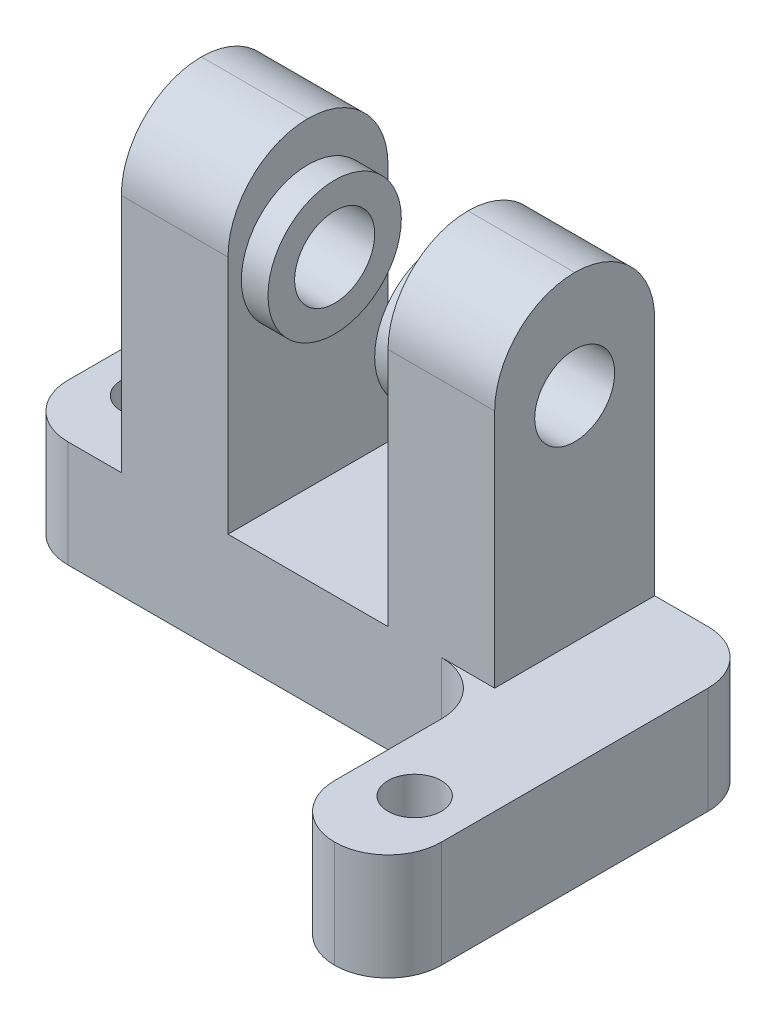
SolidWorks part; units mm, degrees
ref_plane "Front Plane" through (0, 0, 0) normal (0, 0, 1) x (1, 0, 0)
ref_plane "Top Plane" through (0, 0, 0) normal (0, 1, 0) x (1, 0, 0)
ref_plane "Right Plane" through (0, 0, 0) normal (1, 0, 0) x (0, 0, -1)
sketch "Sketch2" plane through (0, 0, 0) normal (0, 1, 0) x (1, 0, 0)
  line L1 (-7, 3) -> (7, 3)
  line L2 (-7, 3) -> (-7, -3)
  line L3 (-7, -3) -> (7, -3)
  line L4 (7, 3) -> (7, -3)
  line L5 (-7, 3) -> (7, -3) construction
  line L6 (-7, -3) -> (7, 3) construction
  point P0 (0, 0)
extrude "Boss-Extrude1" add sketch "Sketch2" along normal blind 4
sketch "Sketch3" plane through (0, 4, 0) normal (0, 1, 0) x (1, 0, 0)
  line L0 (-7, -3) -> (-3, -3)
  line L1 (-7, -3) -> (7, -3) construction
  line L2 (-3, -3) -> (-3, 3)
  line L3 (7, 3) -> (-7, 3) construction
  line L4 (-3, 3) -> (-7, 3)
  line L5 (-7, 3) -> (-7, -3)
  line L6 (7, -3) -> (3, -3)
  line L7 (3, -3) -> (3, 3)
  line L8 (3, 3) -> (7, 3)
  line L9 (7, 3) -> (7, -3)
extrude "Boss-Extrude2" add sketch "Sketch3" along normal blind 12
sketch "Sketch4" plane through (7, 0, 0) normal (1, 0, 0) x (0, 0, -1)
  circle A0 centre (0, 12) radius 1.5
extrude "Cut-Extrude1" cut sketch "Sketch4" against normal through all both and the other way through all
sketch "Sketch5" plane through (-3, 0, 0) normal (1, 0, 0) x (0, 0, -1)
  circle A0 centre (0, 12) radius 1.5
  circle A1 centre (0, 12) radius 2.5
extrude "Boss-Extrude3" add sketch "Sketch5" along normal blind 1
sketch "Sketch6" plane through (3, 0, 0) normal (-1, 0, 0) x (0, 0, 1)
  circle A0 centre (0, 12) radius 1.5
  circle A1 centre (0, 12) radius 2.5
extrude "Boss-Extrude4" add sketch "Sketch6" along normal blind 1
sketch "Sketch7" plane through (0, 4, 0) normal (0, 1, 0) x (1, 0, 0)
  line L2 (11, 3) -> (11, -3)
  line L4 (-7, -3) -> (-7, 3)
  line L5 (-7, 3) -> (-7, -3) construction
  line L6 (-7, 3) -> (-11, 3)
  line L7 (-11, 3) -> (-11, -3)
  line L8 (-11, -3) -> (-7, -3)
  line L9 (11, 3) -> (7, 3)
  line L10 (7, 3) -> (7, -3)
  line L11 (11, -3) -> (11, -11)
  line L12 (11, -11) -> (7, -11)
  line L13 (7, -11) -> (7, -3)
  circle A0 centre (9, -8) radius 1
  circle A1 centre (-9, 0) radius 1
extrude "Boss-Extrude5" add sketch "Sketch7" against normal blind 4
fillet "Fillet1" radius 2 6 edges at (-11, 2, -3) (11, 2, -3) (11, 2, 11) (7, 2, 11) (-11, 2, 3) (7, 2, 3)
fillet "Fillet2" radius 3 4 edges at (-5, 16, -3) (5, 16, -3) (5, 16, 3) (-5, 16, 3)
